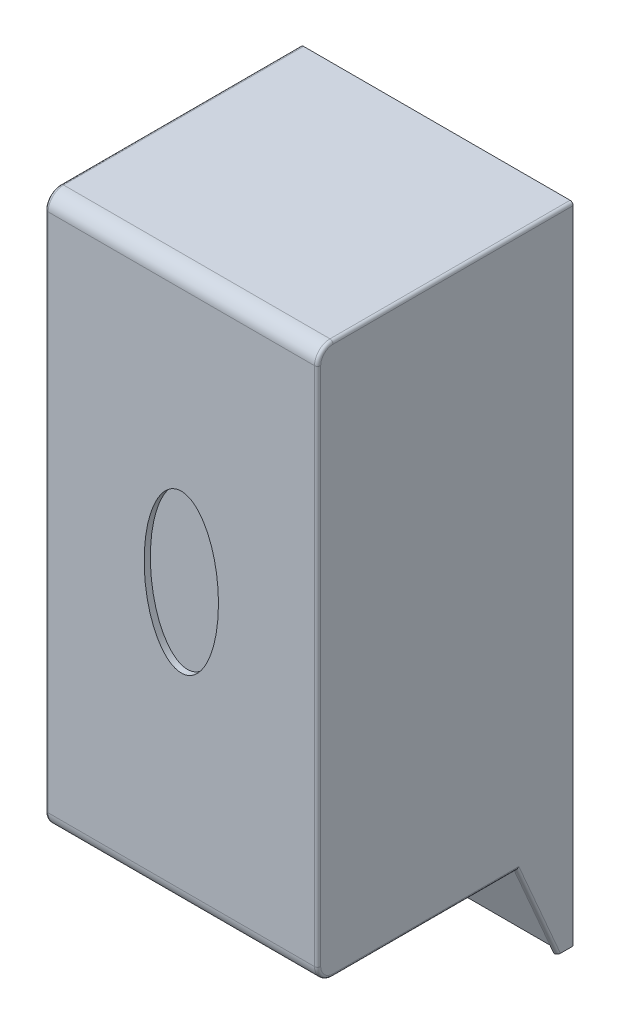
SolidWorks part; units mm, degrees
ref_plane "Front Plane" through (0, 0, 0) normal (0, 0, 1) x (1, 0, 0)
ref_plane "Top Plane" through (0, 0, 0) normal (0, 1, 0) x (1, 0, 0)
ref_plane "Right Plane" through (0, 0, 0) normal (1, 0, 0) x (0, 0, -1)
sketch "Sketch1" plane through (0, 0, 0) normal (0, 0, 1) x (1, 0, 0)
  line L1 (0, 0) -> (111.76, 0)
  line L2 (0, 0) -> (0, 264.16)
  line L3 (0, 264.16) -> (111.76, 264.16)
  line L4 (111.76, 0) -> (111.76, 264.16)
  dimension "D1" = 264.16
  dimension "D2" = 111.76
extrude "Boss-Extrude1" add sketch "Sketch1" along normal blind 104.775
sketch "Sketch2" plane through (0, 0, 104.775) normal (0, 0, 1) x (1, 0, 0)
  line L0 (111.76, 0) -> (111.76, 264.16) construction
  line L1 (0, 0) -> (111.76, 0)
  line L2 (0, 0) -> (0, 38.1)
  line L3 (0, 38.1) -> (111.76, 38.1)
  line L4 (111.76, 0) -> (111.76, 38.1)
extrude "Cut-Extrude1" cut sketch "Sketch2" against normal blind 81.661
ref_plane "Plane1" through (0, 0, 0) normal (0, -1, 0) x (-1, 0, 0)
sketch "Sketch5" plane through (0, 0, 0) normal (0, -1, 0) x (-1, 0, 0)
  line L0 (0, -23.114) -> (0, 0) construction
  line L1 (-111.76, -23.114) -> (0, -23.114)
  line L2 (-111.76, -23.114) -> (-111.76, -6.5962)
  line L3 (-111.76, -6.5962) -> (0, -6.5962)
  line L4 (0, -23.114) -> (0, -6.5962)
loft "Cut-Loft3" cut profiles "Sketch5" section face at (55.88, 19.05, 23.114) section "Sketch5"
sketch "Sketch7" plane through (0, 0, 0) normal (0, 0, -1) x (-1, 0, 0)
  line L0 (-13.6137, 0) -> (13.6137, 0) construction
  line L1 (-110.49, 0) -> (-1.27, 0)
  line L2 (-110.49, 0) -> (-110.49, 3.7935)
  line L3 (-110.49, 3.7935) -> (-1.27, 3.7935)
  line L4 (-1.27, 0) -> (-1.27, 3.7935)
  line L5 (0, 264.16) -> (0, 0) construction
  line L6 (-111.76, 0) -> (-111.76, 264.16) construction
  dimension "D1" = 1.27
  dimension "D2" = 1.27
extrude "Cut-Extrude3" cut sketch "Sketch7" against normal through all
sketch "Sketch8" plane through (0, 0, 104.775) normal (0, 0, 1) x (1, 0, 0)
  line L1 (0, 264.16) -> (0, 38.1) construction
  ellipse E0 centre (55.88, 153.6635) end of major axis (55.88, 185.9517) minor radius 15.2372
  dimension "D1" = 55.88
extrude "Cut-Extrude4" cut sketch "Sketch8" against normal blind 2.54
sketch "Sketch9" plane through (0, 38.1, 0) normal (0, -1, 0) x (1, 0, 0)
  line L0 (0, 23.114) -> (0, 104.775) construction
  circle A0 centre (55.88, 64.4027) radius 5.0405
  dimension "D1" = 55.88
extrude "Boss-Extrude2" add sketch "Sketch9" along normal blind 6.35
sketch "Sketch10" plane through (0, 31.75, 0) normal (0, -1, 0) x (1, 0, 0)
  circle A0 centre (55.88, 64.4027) radius 2.3982
extrude "Boss-Extrude3" add sketch "Sketch10" along normal blind 2.54
fillet "Fillet1" radius 6.35 2 edges at (55.88, 264.16, 104.775) (55.88, 38.1, 104.775)
fillet "Fillet2" radius 1.27 12 edges at (0, 264.16, 49.2125) (0, 262.3001, 102.9151) (0, 39.9599, 102.9151) (111.76, 39.9599, 102.9151) (111.76, 264.16, 49.2125) (111.76, 262.3001, 102.9151) (0, 151.13, 104.775) (111.76, 151.13, 104.775)
